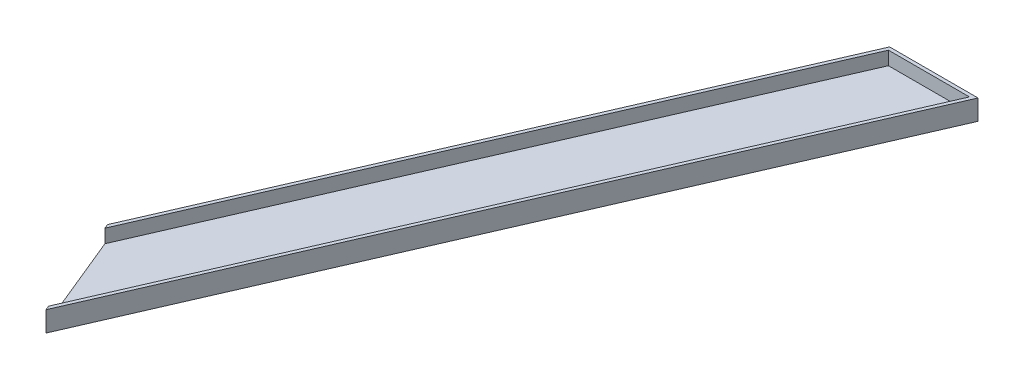
SolidWorks part; units mm, degrees
ref_plane "前基準面" through (0, 0, 0) normal (0, 0, 1) x (1, 0, 0)
ref_plane "上基準面" through (0, 0, 0) normal (0, 1, 0) x (1, 0, 0)
ref_plane "右基準面" through (0, 0, 0) normal (1, 0, 0) x (0, 0, -1)
sketch "草圖1" plane through (0, 0, 0) normal (0, 1, 0) x (1, 0, 0)
  line L0 (0, 0) -> (-5.8292, 14.1707)
  line L1 (0, 0) -> (285.4904, 0) construction
  line L2 (-5.8292, 14.1707) -> (29.5676, 95.5)
  line L3 (0, 0) -> (41.5642, 95.5)
  line L4 (41.5642, 95.5) -> (29.5676, 95.5)
  dimension "D1" = 67.64
  dimension "D2" = 66.48
  dimension "D3" = 11
  dimension "D4" = 95.5
extrude "填料-伸長1" add sketch "草圖1" along normal blind 1 contours L3 L4 L2 L0
sketch "草圖2" plane through (0, 1, 0) normal (0, 1, 0) x (1, 0, 0)
  line L0 (-5.8292, 14.1707) -> (29.5676, 95.5) construction
  line L1 (0, 0) -> (41.5642, 95.5) construction
  line L2 (-5.8292, 14.1707) -> (29.5676, 95.5)
  line L3 (0, 0) -> (41.5642, 95.5)
  line L4 (41.5642, 95.5) -> (42.1095, 95.5)
  line L5 (42.1095, 95.5) -> (0.265, -0.6441)
  line L6 (0, 0) -> (0.265, -0.6441)
  line L8 (0, 0) -> (-5.8292, 14.1707) construction
  line L9 (29.5676, 95.5) -> (29.0222, 95.5)
  line L10 (29.0222, 95.5) -> (-6.0941, 14.8149)
  line L11 (-5.8292, 14.1707) -> (-6.0941, 14.8149)
  dimension "D1" = 0.5
  dimension "D2" = 0.5
extrude "填料-伸長2" add sketch "草圖2" along normal blind 2 and the other way blind 1 separate body contours L5 L6 L3 L4
extrude "填料-伸長4" add sketch "草圖2<4>" along normal blind 2 and the other way blind 1 contours L10 L11 L2 L9
sketch "草圖2<4>" plane through (0, 1, 0) normal (0, 1, 0) x (1, 0, 0) same geometry as "草圖2"
sketch "草圖7" plane through (0, 1, 0) normal (0, 1, 0) x (1, 0, 0)
  line L0 (41.5642, 95.5) -> (29.5676, 95.5) construction
  line L1 (41.5642, 95.5) -> (29.5676, 95.5)
  line L2 (29.5676, 95.5) -> (29.3499, 95)
  line L3 (-5.8292, 14.1707) -> (29.5676, 95.5) construction
  line L4 (29.3499, 95) -> (41.3466, 95)
  line L5 (0, 0) -> (41.5642, 95.5) construction
  line L6 (41.3466, 95) -> (41.5642, 95.5)
  dimension "D1" = 0.5
extrude "填料-伸長5" add sketch "草圖7" along normal up to surface (2 mm away) contours L4 L6 L1 L2 up to face at (11.6666, 3, -54.9964)
